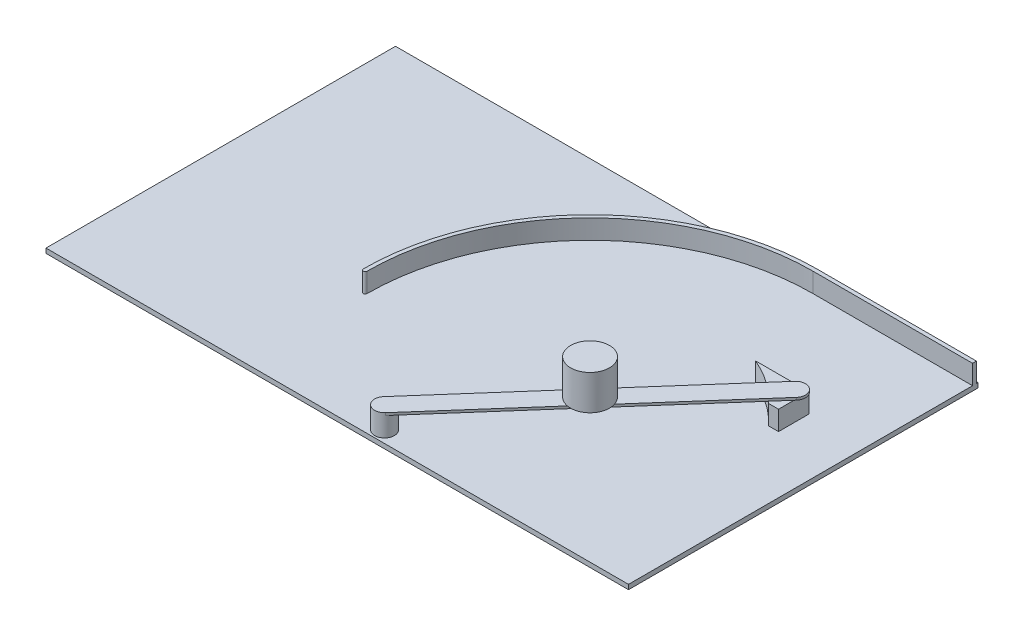
SolidWorks part; units mm, degrees
ref_plane "Front Plane" through (0, 0, 0) normal (0, 0, 1) x (1, 0, 0)
ref_plane "Top Plane" through (0, 0, 0) normal (0, 1, 0) x (1, 0, 0)
ref_plane "Right Plane" through (0, 0, 0) normal (1, 0, 0) x (0, 0, -1)
sketch "Sketch1" plane through (0, 0, 0) normal (0, 1, 0) x (1, 0, 0)
  line L1 (750, -450) -> (-750, -450)
  line L2 (750, -450) -> (750, 450)
  line L3 (750, 450) -> (-750, 450)
  line L4 (-750, -450) -> (-750, 450)
  line L5 (750, -450) -> (-750, 450) construction
  line L6 (750, 450) -> (-750, -450) construction
  point P0 (0, 0)
  dimension "D1" = 900
  dimension "D2" = 1500
extrude "Boss-Extrude1" add sketch "Sketch1" along normal blind 12
sketch "Sketch2" plane through (0, 12, 0) normal (0, 1, 0) x (1, 0, 0)
  line L0 (-750, -450) -> (750, -450) construction
  line L1 (339, 436) -> (750, 436)
  line L4 (750, -450) -> (750, 450) construction
  line L5 (339, 446) -> (750, 446)
  line L6 (750, 446) -> (750, 436)
  circle A0 centre (339, -138) radius 300
  arc A1 (339, 436) -> (-235, -138) centre (339, -138) ccw
  arc A2 (339, 446) -> (-245, -138) centre (339, -138) ccw
  arc A4 (-235, -138) -> (-245, -138) centre (-240, -138) cw
  point P7 (339, -138)
  dimension "D1" = 600
  dimension "D2" = 312
  dimension "D3" = 274
  dimension "D4" = 411
  dimension "D5" = 10
extrude "Boss-Extrude2" add sketch "Sketch2" along normal blind 50 contours A1 A4 A2 L5 L6 L1
sketch "Sketch3" plane through (0, 12, 0) normal (0, 1, 0) x (1, 0, 0)
  line L1 (602.5327, 162) -> (465.0363, 162)
  line L2 (602.5327, 162) -> (602.5327, 83.761)
  line L3 (602.5327, 83.761) -> (577.1327, 83.761)
  arc A0 (465.0363, 162) -> (577.1327, 83.761) centre (339, -138) cw
  circle A1 centre (339, -138) radius 300 construction
  dimension "D1" = 25.4
  dimension "D2" = 25.4
  dimension "D3" = 78.239
extrude "Boss-Extrude3" add sketch "Sketch3" along normal blind 50
sketch "Sketch4" plane through (0, 62, 0) normal (0, 1, 0) x (1, 0, 0)
  line L0 (91.5119, -419.7351) -> (586.4881, 143.7351) construction
  line L1 (72.4291, -402.9719) -> (567.4052, 160.4983)
  line L2 (110.5948, -436.4983) -> (605.5709, 126.9719)
  line L3 (586.4881, 143.7351) -> (632.7801, 196.433) construction
  arc A1 (72.4291, -402.9719) -> (110.5948, -436.4983) centre (91.5119, -419.7351) ccw
  arc A2 (605.5709, 126.9719) -> (567.4052, 160.4983) centre (586.4881, 143.7351) ccw
  point P2 (339, -138)
  point P4 (339, -138)
  dimension "D1" = 750
  dimension "D2" = 50.8
extrude "Boss-Extrude4" add sketch "Sketch4" along normal blind 6.35
sketch "Sketch5" plane through (0, 12, 0) normal (0, 1, 0) x (1, 0, 0)
  circle A0 centre (91.5119, -419.7351) radius 25.4
  dimension "D1" = 50.8
extrude "Boss-Extrude5" add sketch "Sketch5" along normal up to surface (50 mm away) up to face at (318.2782, 62, 161.5893)
sketch "Sketch6" plane through (0, 68.35, 0) normal (0, 1, 0) x (1, 0, 0)
  circle A0 centre (339, -138) radius 50
  dimension "D1" = 100
extrude "Boss-Extrude6" add sketch "Sketch6" along normal blind 90
equation "\"D2@Sketch2\"=\"D1@Sketch2\"/2+12"
